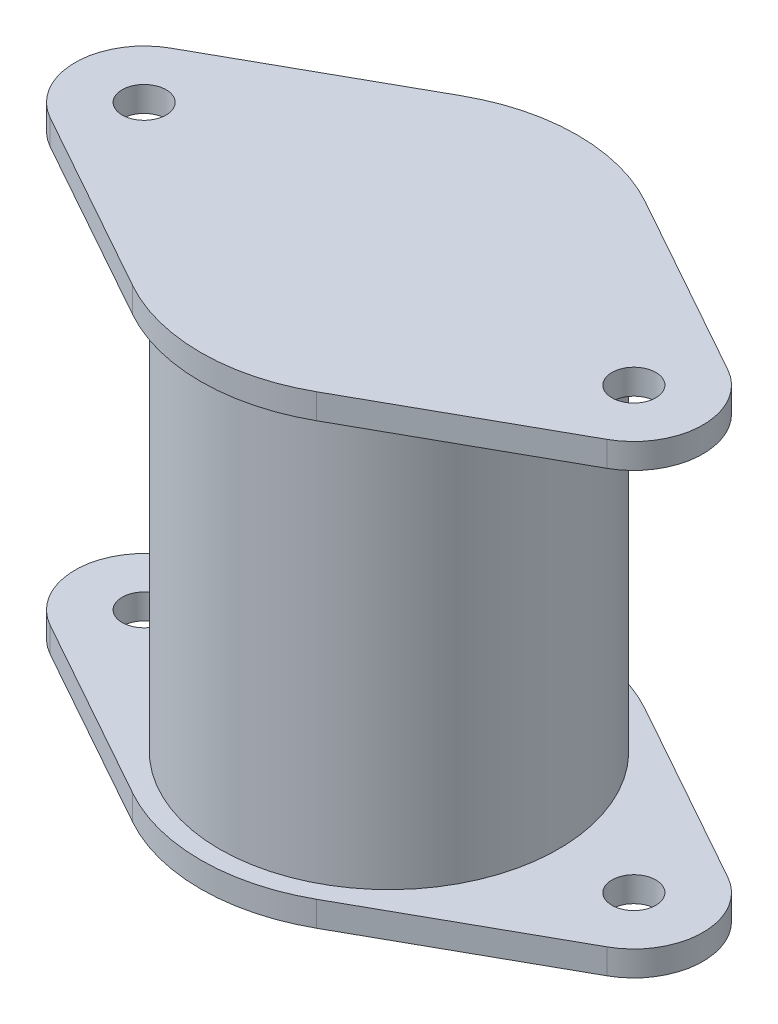
SolidWorks part; units mm, degrees
ref_plane "前视基准面" through (0, 0, 0) normal (0, 0, 1) x (1, 0, 0)
ref_plane "上视基准面" through (0, 0, 0) normal (0, 1, 0) x (1, 0, 0)
ref_plane "右视基准面" through (0, 0, 0) normal (1, 0, 0) x (0, 0, -1)
sketch "草图1" plane through (0, 0, 0) normal (0, 1, 0) x (1, 0, 0)
  line L0 (-22.1795, 4.8032) -> (-7.3077, 13.0995)
  line L1 (-22.1795, -4.8032) -> (-7.3077, -13.0995)
  line L2 (7.3077, -13.0995) -> (22.1795, -4.8032)
  line L3 (22.1795, 4.8032) -> (7.3077, 13.0995)
  circle A0 centre (0, 0) radius 13.5
  circle A1 centre (-19.5, 0) radius 1.75
  arc A3 (-7.3077, 13.0995) -> (7.3077, 13.0995) centre (0, 0) cw
  arc A4 (-22.1795, 4.8032) -> (-22.1795, -4.8032) centre (-19.5, 0) ccw
  circle A5 centre (19.5, 0) radius 1.75
  arc A6 (22.1795, -4.8032) -> (22.1795, 4.8032) centre (19.5, 0) ccw
  arc A7 (-7.3077, -13.0995) -> (7.3077, -13.0995) centre (0, 0) ccw
  dimension "D1" = 19.5
  dimension "D2" = 5.5
  dimension "D3" = 15
  dimension "D4" = 15
  dimension "D5" = 5.5
  dimension "D6" = 39
  dimension "D7" = 3.5
  dimension "D8" = 3.5
  dimension "D9" = 27
extrude "凸台-拉伸1" add sketch "草图1" against normal blind 2 contours L1 A7 L2 A6 L3 A3 L0 A4 A0 A1 A5 | A0 region at (-14.4595, 0, -8.4421) region at (0, 0, 0)
extrude "凸台-拉伸2" add sketch "草图1<3>" along normal blind 16.5 contours A0 region at (0, 0, 0)
sketch "草图1<3>" plane through (0, 0, 0) normal (0, 1, 0) x (1, 0, 0) same geometry as "草图1"
mirror "镜向3" about plane through (0, 16.5, 0) normal (0, 1, 0) of bodies 102
